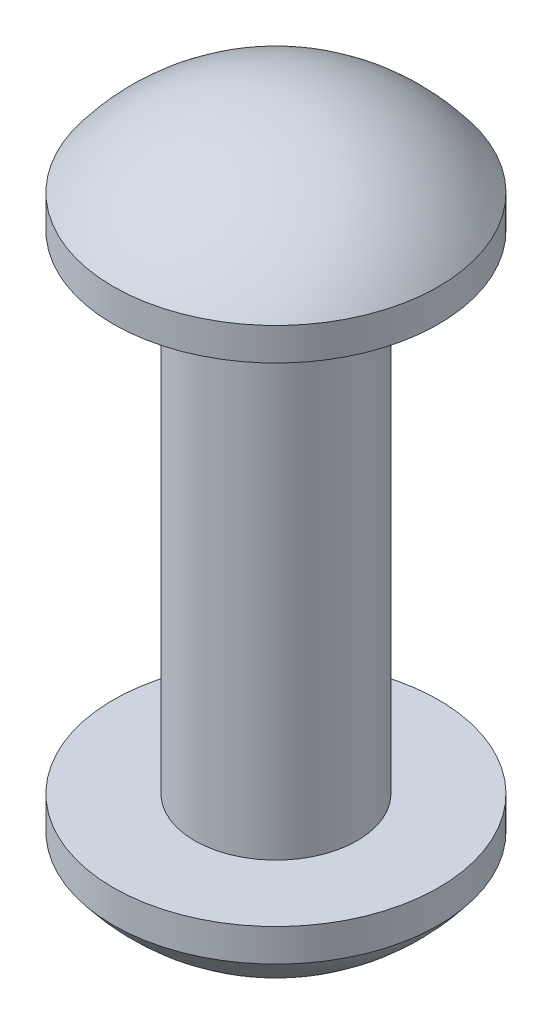
SolidWorks part; units mm, degrees
material "Латунь"
ref_plane "Спереди" through (0, 0, 0) normal (0, 0, 1) x (1, 0, 0)
ref_plane "Сверху" through (0, 0, 0) normal (0, 1, 0) x (1, 0, 0)
ref_plane "Справа" through (0, 0, 0) normal (1, 0, 0) x (0, 0, -1)
sketch "Эскиз1" plane through (0, 0, 0) normal (0, 1, 0) x (1, 0, 0)
  circle A0 centre (0, 0) radius 3
  dimension "D1" = 6
extrude "Бобышка-Вытянуть1" add sketch "Эскиз1" along normal mid plane 18
sketch "Эскиз2" plane through (0, 9, 0) normal (0, 1, 0) x (1, 0, 0)
  circle A2 centre (0, 0) radius 6
  circle A3 centre (0, 0) radius 6
  dimension "D1" = 3
extrude "Бобышка-Вытянуть2" add sketch "Эскиз2" along normal blind 1.2
dome "Купол1" faces to dome 1 distance 3 reverse direction no elliptical dome no face at (0, 10.2, 6) parameters "D1"=3
mirror "Зеркальное отражение1" about plane through (0, 0, 0) normal (0, 1, 0) of "Купол1", "Бобышка-Вытянуть2"
equation "\"длина лезвия\"=1000"
equation "\"радиус острия\"=3"
equation "\"длина острия\"=40"
equation "\"ширина лезвия\"=30"
equation "\"радиус сгиба\"=2"
equation "\"высота ребра жесткости\"=7"
equation "\"толщина лезвия \"=2"
equation "\"длина рукоятки\"=200"
equation "\"тлщина рукоятки\"=30"
equation "\"диаметр заклепки\"=6"
equation "\"расстояние между заклнпками\"=75"
equation "\"глубина заклепки\"=6"
equation "\"отступ от заклепки\"=3"
equation "\"диаметр шляпы\"=\"диаметр заклепки\" + 2*\"отступ от заклепки\""
equation "\"радиус скруглений\"=5"
equation "\"D1@Эскиз1\"=\"диаметр заклепки\""
equation "\"D1@Эскиз2\"=\"отступ от заклепки\""
equation "\"высота головки\"=1.2"
equation "\"высота купола\"=3"
equation "\"D1@Бобышка-Вытянуть2\"=\"высота головки\""
equation "\"D1@Купол1\"=\"высота купола\""
equation "\"D1@Бобышка-Вытянуть1\"=\"тлщина рукоятки\" - 2 * \"глубина заклепки\""
